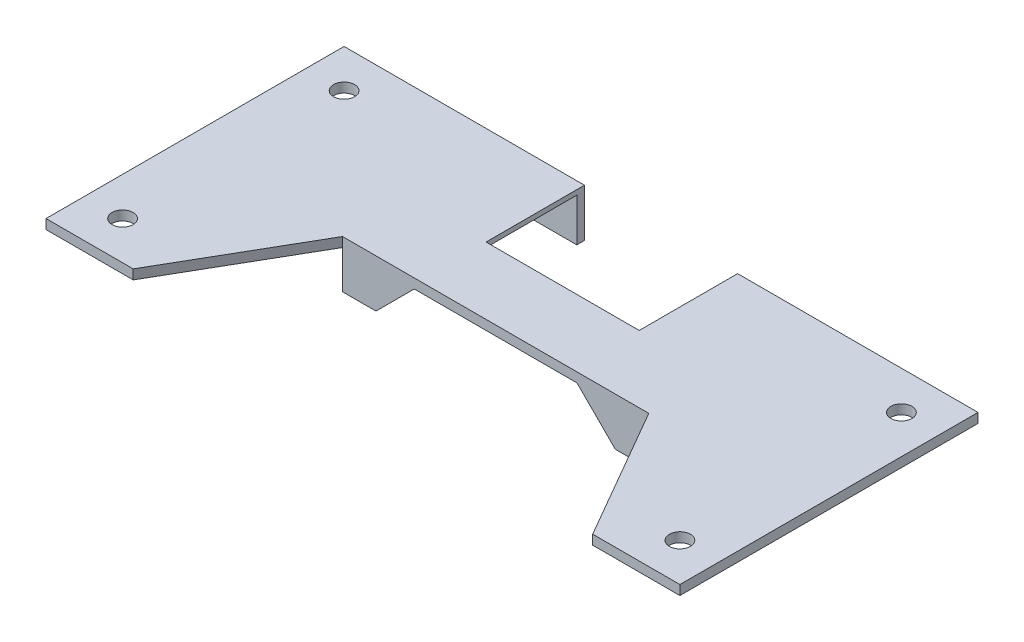
SolidWorks part; units mm, degrees
ref_plane "Front Plane" through (0, 0, 0) normal (0, 0, 1) x (1, 0, 0)
ref_plane "Top Plane" through (0, 0, 0) normal (0, 1, 0) x (1, 0, 0)
ref_plane "Right Plane" through (0, 0, 0) normal (1, 0, 0) x (0, 0, -1)
sketch "Sketch1" plane through (0, 0, 0) normal (0, 1, 0) x (1, 0, 0)
  line L0 (-40.5, 8.3246) -> (-40.5, -22.8154)
  line L1 (-36.5, 4.3246) -> (21.72, 4.3246)
  line L2 (-36.5, 4.3246) -> (-36.5, -18.8154)
  line L3 (-36.5, -18.8154) -> (21.72, -18.8154)
  line L4 (21.72, 4.3246) -> (21.72, -18.8154)
  line L5 (-40.5, -22.8154) -> (25.72, -22.8154)
  line L6 (25.72, 8.3246) -> (25.72, -22.8154)
  line L7 (-40.5, 8.3246) -> (25.72, 8.3246)
  line L8 (-7.39, 8.3246) -> (-7.39, -22.8154) construction
  line L9 (-15.39, 8.3246) -> (-15.39, -22.8154)
  line L10 (-23.39, 8.3246) -> (-23.39, -22.8154)
  line L11 (8.61, 8.3246) -> (8.61, -22.8154)
  line L12 (0.61, 8.3246) -> (0.61, -22.8154)
  line L13 (-40.5, 7.5246) -> (25.72, 7.5246)
  line L14 (-23.39, -7.2454) -> (-15.39, -7.2454)
  line L15 (0.61, -7.2454) -> (8.61, -7.2454)
  line L16 (8.61, -8.9554) -> (-23.39, -8.9554)
  line L17 (0.61, -1.9554) -> (-15.39, -1.9554)
  circle A0 centre (-36.5, 4.3246) radius 1.1
  circle A1 centre (-36.5, -18.8154) radius 1.1
  circle A2 centre (21.72, -18.8154) radius 1.1
  circle A3 centre (21.72, 4.3246) radius 1.1
  dimension "D3" = 4
  dimension "D1" = 58.22
  dimension "D2" = 23.14
  dimension "D4" = 8
  dimension "D5" = 8
  dimension "D6" = 0.8
  dimension "D7" = 1.71
  dimension "D8" = 7
extrude "Boss-Extrude1" add sketch "Sketch1" along normal blind 1 contours A1 L3 L10 L1 A0 L2 | A1 L2 A0 L1 L10 L7 L0 L5 L3 | A3 L1 L11 L3 A2 L4 | A3 L4 A2 L3 L11 L5 L6 L7 L1 | L0 L13 L10 L7 | L11 L13 L6 L7 | L17 L8 L16 L12 | L8 L17 L9 L16 region at (-31.945, 0, -7.9246) region at (-31.945, 0, -7.1763) region at (-29.9066, 0, 7.2454) region at (-11.39, 0, 5.4554) region at (17.165, 0, -7.9246) region at (-3.39, 0, 5.4554) region at (17.165, 0, -7.1763) region at (15.1266, 0, 7.2454)
extrude "Boss-Extrude2" add sketch "Sketch1<3>" against normal blind 5 from surface contours L7 L10 L1 L9 | L7 L12 L1 L11 | L10 L14 L9 L1 | L12 L15 L11 L1 | L16 L11 L15 L12 | L16 L9 L14 L10 region at (-19.39, 0, -5.9246) region at (-19.39, 0, 1.4604) region at (-19.39, 0, 8.1004) region at (4.61, 0, -5.9246) region at (4.61, 0, 1.4604) region at (4.61, 0, 8.1004) starting at face at (-31.945, 1, 7.2454)
sketch "Sketch1<3>" plane through (0, 0, 0) normal (0, 1, 0) x (1, 0, 0) same geometry as "Sketch1"
chamfer "Chamfer1" distance 4.5 angle 45 1 edges at (0.61, -4, 0.7154)
chamfer "Chamfer2" distance 4.5 angle 45 1 edges at (-15.39, -4, 0.7154)
extrude "Boss-Extrude3" add sketch "Sketch1<4>" along direction (0, 1, 0) on the side against the normal up to surface (4 mm away) from surface contours L10 L13 L9 L7 | L12 L13 L11 L7 region at (-19.39, 0, -7.9246) region at (4.61, 0, -7.9246) up to face at (-21.64, -4, 0.7154) starting at face at (-7.39, 1, 3.1054)
sketch "Sketch1<4>" plane through (0, 0, 0) normal (0, 1, 0) x (1, 0, 0) same geometry as "Sketch1"
chamfer "Chamfer3" distance 8 angle 60 1 edges at (-23.39, 0.5, 22.8154) first distance on face at (-31.945, 0.5, 22.8154)
chamfer "Chamfer4" distance 8 angle 60 1 edges at (8.61, 0.5, 22.8154) first distance on face at (17.165, 0.5, 22.8154)
